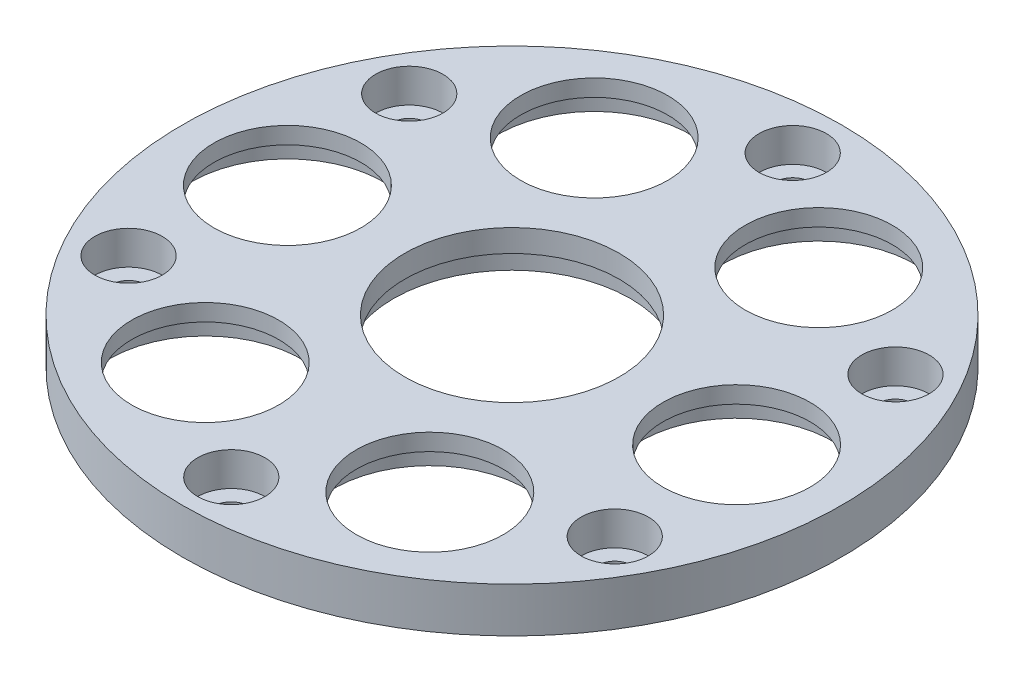
SolidWorks part; units mm, degrees
ref_plane "Front Plane" through (0, 0, 0) normal (0, 0, 1) x (1, 0, 0)
ref_plane "Top Plane" through (0, 0, 0) normal (0, 1, 0) x (1, 0, 0)
ref_plane "Right Plane" through (0, 0, 0) normal (1, 0, 0) x (0, 0, -1)
sketch "Sketch1" plane through (0, 0, 0) normal (0, 1, 0) x (1, 0, 0)
  line L0 (0, 0) -> (-20, 0) construction
  line L1 (-28.55, 0) -> (-29.35, 0) construction
  line L2 (0, 0) -> (0, 25) construction
  circle A0 centre (0, 0) radius 10.55
  circle A1 centre (-20, 0) radius 8.55
  circle A2 centre (0, 0) radius 9.55
  circle A3 centre (-20, 0) radius 6.55
  circle A4 centre (0, 0) radius 29.35
  circle A5 centre (-10, 17.3205) radius 8.55
  circle A6 centre (-10, 17.3205) radius 6.55
  circle A7 centre (10, 17.3205) radius 8.55
  circle A8 centre (10, 17.3205) radius 6.55
  circle A9 centre (20, 0) radius 8.55
  circle A10 centre (20, 0) radius 6.55
  circle A11 centre (10, -17.3205) radius 8.55
  circle A12 centre (10, -17.3205) radius 6.55
  circle A13 centre (-10, -17.3205) radius 8.55
  circle A14 centre (-10, -17.3205) radius 6.55
  circle A15 centre (0, 25) radius 1.55
  circle A16 centre (0, 25) radius 3
  circle A17 centre (21.6506, 12.5) radius 3
  circle A18 centre (21.6506, 12.5) radius 1.55
  circle A19 centre (21.6506, -12.5) radius 3
  circle A20 centre (21.6506, -12.5) radius 1.55
  circle A21 centre (0, -25) radius 3
  circle A22 centre (0, -25) radius 1.55
  circle A23 centre (-21.6506, -12.5) radius 3
  circle A24 centre (-21.6506, -12.5) radius 1.55
  circle A25 centre (-21.6506, 12.5) radius 3
  circle A26 centre (-21.6506, 12.5) radius 1.55
  dimension "D1" = 21.1
  dimension "D2" = 17.1
  dimension "D8" = 3.1
  dimension "D9" = 6
  dimension "D3" = 20
  dimension "D4" = 0.8
  dimension "D5" = 2
  dimension "D6" = 1
  dimension "D10" = 25
  dimension "D7" = 6
extrude "Boss-Extrude1" add sketch "Sketch1" against normal blind 4 contours A4
extrude "Cut-Extrude1" cut sketch "Sketch1<4>" against normal through all contours A3 | A14 | A12 | A10 | A8 | A6 | A24 | A22 | A20 | A18 | A15 | A26 | A2 region at (0, 0, 0) region at (-20, 0, 0) region at (-10, 0, -17.3205) region at (10, 0, -17.3205) region at (20, 0, 0) region at (10, 0, 17.3205) region at (-10, 0, 17.3205) region at (0, 0, -25) region at (21.6506, 0, -12.5) region at (21.6506, 0, 12.5) region at (0, 0, 25) region at (-21.6506, 0, 12.5) region at (-21.6506, 0, -12.5)
sketch "Sketch1<4>" plane through (0, 0, 0) normal (0, 1, 0) x (1, 0, 0) same geometry as "Sketch1"
extrude "Cut-Extrude2" cut sketch "Sketch1<5>" against normal through all from offset 1.5 contours A1 A3 | A5 A6 | A7 A8 | A9 A10 | A11 A12 | A13 A14 region at (-28.3082, 0, 0) region at (-18.3082, 0, -17.3205) region at (1.6918, 0, -17.3205) region at (11.6918, 0, 0) region at (1.6918, 0, 17.3205) region at (-18.3082, 0, 17.3205) offset against normal yes
sketch "Sketch1<5>" plane through (0, 0, 0) normal (0, 1, 0) x (1, 0, 0) same geometry as "Sketch1"
extrude "Cut-Extrude3" cut sketch "Sketch1<6>" against normal through all from offset 2 contours A0 A2 region at (-10.2516, 0, 0) offset against normal yes
sketch "Sketch1<6>" plane through (0, 0, 0) normal (0, 1, 0) x (1, 0, 0) same geometry as "Sketch1"
extrude "Cut-Extrude4" cut sketch "Sketch1<7>" against normal blind 3 contours A25 A26 | A16 A15 | A17 A18 | A19 A20 | A21 A22 | A23 A24 region at (-2.9151, 0, -25) region at (18.7355, 0, -12.5) region at (18.7355, 0, 12.5) region at (-2.9151, 0, 25) region at (-24.5658, 0, 12.5) region at (-24.5658, 0, -12.5)
sketch "Sketch1<7>" plane through (0, 0, 0) normal (0, 1, 0) x (1, 0, 0) same geometry as "Sketch1"
equation "\"Ratio\"= 15"
equation "\"Hull Diameter\"= 3.5in"
equation "\"Fixed Ring Diameter\"= 76"
equation "\"Fixed Pin Diameter\"= 6"
equation "\"Output Ring Diameter\"= 40"
equation "\"Output Pin Diameter\"= 6"
equation "\"Disk Bearing Inner Diameter\"= 9"
equation "\"Disk Bearing Outer Diameter\"= 17"
equation "\"Disk Bearing Height\"= 5"
equation "\"Shaft Bearing Inner Diameter\"= 15"
equation "\"Shaft Bearing Outer Diameter\"= 21"
equation "\"Shaft Bearing Height\"= 4"
equation "\"Eccentricity\"= 1.5"
equation "\"Disk Height\"= 8"
equation "\"Disk Spacing\"= 5"
equation "\"Hull Height\"= 40"
equation "\"Shaft End Bearing Inner Diameter\"= 12"
equation "\"Shaft End Bearing Outer Diameter\"= 18"
equation "\"Shaft End Bearing Height\"= 4"
equation "\"Output Bearing Inner Diameter\"= 55"
equation "\"Output Bearing Outer Diameter\"= 72"
equation "\"Outer Bearing Height\"= 9"
equation "\"D1@Sketch1\"=\"Shaft Bearing Outer Diameter\"+0.1"
equation "\"D2@Sketch1\"=\"Disk Bearing Outer Diameter\"+0.1"
equation "\"D3@Sketch1\"=\"Output Ring Diameter\"/2"
